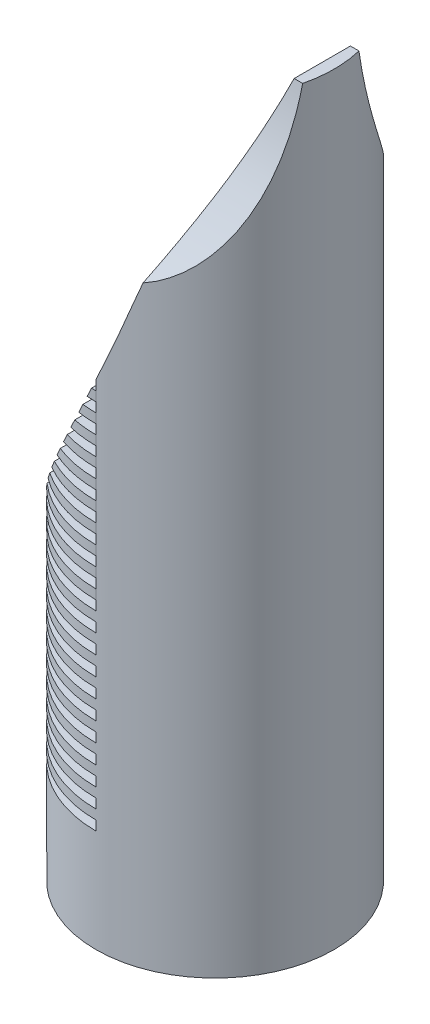
SolidWorks part; units mm, degrees
ref_plane "Front Plane" through (0, 0, 0) normal (0, 0, 1) x (1, 0, 0)
ref_plane "Top Plane" through (0, 0, 0) normal (0, 1, 0) x (1, 0, 0)
ref_plane "Right Plane" through (0, 0, 0) normal (1, 0, 0) x (0, 0, -1)
sketch "Sketch1" plane through (0, 0, 0) normal (0, 1, 0) x (1, 0, 0)
  circle A0 centre (0, 0) radius 2.5
  circle A1 centre (0, 0) radius 0.5
  dimension "D1" = 5
  dimension "D2" = 1
extrude "Boss-Extrude1" add sketch "Sketch1" along normal blind 2
sketch "Sketch2" plane through (0, 2, 0) normal (0, 1, 0) x (1, 0, 0)
  circle A0 centre (0, 0) radius 2.5
  dimension "D1" = 5
extrude "Boss-Extrude2" add sketch "Sketch2" along normal blind 14
sketch "Sketch3" plane through (0, 0, 0) normal (0, 0, 1) x (1, 0, 0)
  line L0 (0, 16) -> (0, 6) construction
  line L1 (2.5, 16) -> (-2.5, 16) construction
  line L2 (-2.5, 16) -> (-2.5, 0) construction
  line L3 (1.5, 16) -> (-2.5, 16)
  line L4 (-2.5, 16) -> (-2.5, 6)
  spline S0 degree 3 poles (1.5, 16) (1.3118, 12.2915) (-0.5237, 8.9999) (-2.5, 6) knots 0 0 0 0 1 1 1 1
  dimension "D1" = 10
extrude "Cut-Extrude1" cut sketch "Sketch3" against normal through all both and the other way through all
sketch "Sketch4" plane through (0, 2, 0) normal (0, -1, 0) x (1, 0, 0)
  circle A0 centre (0, 0) radius 0.5
extrude "Cut-Extrude2" cut sketch "Sketch4" against normal blind 7
sketch "Sketch5" plane through (0, 0, 0) normal (1, 0, 0) x (0, 0, -1)
  line L0 (0, 0) -> (0, 10.3563) construction
  line L1 (-2.5, 0) -> (2.5, 0) construction
  line L2 (3.1377, 10.1563) -> (0.25, 10.1563)
  line L3 (0.25, 0) -> (0.25, 10.3563)
  line L4 (-0.25, 0) -> (-0.25, 10.3563)
  line L5 (0.25, 10.3563) -> (3.1377, 10.3563)
  line L6 (3.1377, 9.3563) -> (0.25, 9.3563)
  line L7 (0.25, 0) -> (0.25, 16) construction
  line L8 (0, 0) -> (0, 16) construction
  line L9 (-0.25, 0) -> (-0.25, 16) construction
  line L10 (3.1377, 10.3563) -> (3.1377, 10.1563)
  line L11 (0.25, 9.5563) -> (3.1377, 9.5563)
  line L12 (3.1377, 9.5563) -> (3.1377, 9.3563)
  line L13 (3.1377, 9.7563) -> (0.25, 9.7563)
  line L14 (0.25, 9.9563) -> (3.1377, 9.9563)
  line L15 (3.1377, 9.9563) -> (3.1377, 9.7563)
  line L16 (3.1377, 6.1563) -> (0.25, 6.1563)
  line L17 (0.25, 6.3563) -> (3.1377, 6.3563)
  line L18 (3.1377, 6.3563) -> (3.1377, 6.1563)
  line L19 (3.1377, 6.9563) -> (0.25, 6.9563)
  line L20 (0.25, 7.1563) -> (3.1377, 7.1563)
  line L21 (3.1377, 7.1563) -> (3.1377, 6.9563)
  line L22 (3.1377, 7.3563) -> (0.25, 7.3563)
  line L23 (0.25, 7.5563) -> (3.1377, 7.5563)
  line L24 (3.1377, 7.5563) -> (3.1377, 7.3563)
  line L25 (3.1377, 7.7563) -> (0.25, 7.7563)
  line L26 (0.25, 7.9563) -> (3.1377, 7.9563)
  line L27 (3.1377, 7.9563) -> (3.1377, 7.7563)
  line L28 (3.1377, 8.5563) -> (0.25, 8.5563)
  line L29 (0.25, 8.7563) -> (3.1377, 8.7563)
  line L30 (3.1377, 8.7563) -> (3.1377, 8.5563)
  line L31 (3.1377, 8.9563) -> (0.25, 8.9563)
  line L32 (0.25, 9.1563) -> (3.1377, 9.1563)
  line L33 (3.1377, 9.1563) -> (3.1377, 8.9563)
  line L34 (3.1377, 8.1563) -> (0.25, 8.1563)
  line L35 (0.25, 8.3563) -> (3.1377, 8.3563)
  line L36 (3.1377, 8.3563) -> (3.1377, 8.1563)
  line L37 (3.1377, 2.9563) -> (0.25, 2.9563)
  line L38 (0.25, 3.1563) -> (3.1377, 3.1563)
  line L39 (3.1377, 3.1563) -> (3.1377, 2.9563)
  line L40 (3.1377, 6.5563) -> (0.25, 6.5563)
  line L41 (0.25, 6.7563) -> (3.1377, 6.7563)
  line L42 (3.1377, 6.7563) -> (3.1377, 6.5563)
  line L43 (3.1377, 3.3563) -> (0.25, 3.3563)
  line L44 (0.25, 3.5563) -> (3.1377, 3.5563)
  line L45 (3.1377, 3.5563) -> (3.1377, 3.3563)
  line L46 (3.1377, 4.9563) -> (0.25, 4.9563)
  line L47 (0.25, 5.1563) -> (3.1377, 5.1563)
  line L48 (3.1377, 5.1563) -> (3.1377, 4.9563)
  line L49 (3.1377, 4.5563) -> (0.25, 4.5563)
  line L50 (0.25, 4.7563) -> (3.1377, 4.7563)
  line L51 (3.1377, 4.7563) -> (3.1377, 4.5563)
  line L52 (3.1377, 3.7563) -> (0.25, 3.7563)
  line L53 (0.25, 3.9563) -> (3.1377, 3.9563)
  line L54 (3.1377, 3.9563) -> (3.1377, 3.7563)
  line L55 (3.1377, 4.1563) -> (0.25, 4.1563)
  line L56 (0.25, 4.3563) -> (3.1377, 4.3563)
  line L57 (3.1377, 4.3563) -> (3.1377, 4.1563)
  line L58 (3.1377, 5.3563) -> (0.25, 5.3563)
  line L59 (0.25, 5.5563) -> (3.1377, 5.5563)
  line L60 (3.1377, 5.5563) -> (3.1377, 5.3563)
  line L61 (-3.1377, 2.7563) -> (-3.1377, 2.5563)
  line L62 (-0.25, 2.7563) -> (-3.1377, 2.7563)
  line L63 (-3.1377, 2.5563) -> (-0.25, 2.5563)
  line L64 (-3.1377, 2.3563) -> (-3.1377, 2.1563)
  line L65 (-0.25, 2.3563) -> (-3.1377, 2.3563)
  line L66 (-3.1377, 2.1563) -> (-0.25, 2.1563)
  line L67 (3.1377, 5.7563) -> (0.25, 5.7563)
  line L68 (0.25, 5.9563) -> (3.1377, 5.9563)
  line L69 (3.1377, 5.9563) -> (3.1377, 5.7563)
  line L70 (-3.1377, 5.9563) -> (-3.1377, 5.7563)
  line L71 (-0.25, 5.9563) -> (-3.1377, 5.9563)
  line L72 (-3.1377, 5.7563) -> (-0.25, 5.7563)
  line L73 (3.1377, 2.1563) -> (0.25, 2.1563)
  line L74 (0.25, 2.3563) -> (3.1377, 2.3563)
  line L75 (3.1377, 2.3563) -> (3.1377, 2.1563)
  line L76 (3.1377, 2.5563) -> (0.25, 2.5563)
  line L77 (0.25, 2.7563) -> (3.1377, 2.7563)
  line L78 (3.1377, 2.7563) -> (3.1377, 2.5563)
  line L79 (-3.1377, 5.5563) -> (-3.1377, 5.3563)
  line L80 (-0.25, 5.5563) -> (-3.1377, 5.5563)
  line L81 (-3.1377, 5.3563) -> (-0.25, 5.3563)
  line L82 (-3.1377, 4.3563) -> (-3.1377, 4.1563)
  line L83 (-0.25, 4.3563) -> (-3.1377, 4.3563)
  line L84 (-3.1377, 4.1563) -> (-0.25, 4.1563)
  line L85 (-3.1377, 3.9563) -> (-3.1377, 3.7563)
  line L86 (-0.25, 3.9563) -> (-3.1377, 3.9563)
  line L87 (-3.1377, 3.7563) -> (-0.25, 3.7563)
  line L88 (-3.1377, 4.7563) -> (-3.1377, 4.5563)
  line L89 (-0.25, 4.7563) -> (-3.1377, 4.7563)
  line L90 (-3.1377, 4.5563) -> (-0.25, 4.5563)
  line L91 (-3.1377, 5.1563) -> (-3.1377, 4.9563)
  line L92 (-0.25, 5.1563) -> (-3.1377, 5.1563)
  line L93 (-3.1377, 4.9563) -> (-0.25, 4.9563)
  line L94 (-3.1377, 3.5563) -> (-3.1377, 3.3563)
  line L95 (-0.25, 3.5563) -> (-3.1377, 3.5563)
  line L96 (-3.1377, 3.3563) -> (-0.25, 3.3563)
  line L97 (-3.1377, 6.7563) -> (-3.1377, 6.5563)
  line L98 (-0.25, 6.7563) -> (-3.1377, 6.7563)
  line L99 (-3.1377, 6.5563) -> (-0.25, 6.5563)
  line L100 (-3.1377, 3.1563) -> (-3.1377, 2.9563)
  line L101 (-0.25, 3.1563) -> (-3.1377, 3.1563)
  line L102 (-3.1377, 2.9563) -> (-0.25, 2.9563)
  line L103 (-3.1377, 8.3563) -> (-3.1377, 8.1563)
  line L104 (-0.25, 8.3563) -> (-3.1377, 8.3563)
  line L105 (-3.1377, 8.1563) -> (-0.25, 8.1563)
  line L106 (-3.1377, 9.1563) -> (-3.1377, 8.9563)
  line L107 (-0.25, 9.1563) -> (-3.1377, 9.1563)
  line L108 (-3.1377, 8.9563) -> (-0.25, 8.9563)
  line L109 (-3.1377, 8.7563) -> (-3.1377, 8.5563)
  line L110 (-0.25, 8.7563) -> (-3.1377, 8.7563)
  line L111 (-3.1377, 8.5563) -> (-0.25, 8.5563)
  line L112 (-3.1377, 7.9563) -> (-3.1377, 7.7563)
  line L113 (-0.25, 7.9563) -> (-3.1377, 7.9563)
  line L114 (-3.1377, 7.7563) -> (-0.25, 7.7563)
  line L115 (-3.1377, 7.5563) -> (-3.1377, 7.3563)
  line L116 (-0.25, 7.5563) -> (-3.1377, 7.5563)
  line L117 (-3.1377, 7.3563) -> (-0.25, 7.3563)
  line L118 (-3.1377, 7.1563) -> (-3.1377, 6.9563)
  line L119 (-0.25, 7.1563) -> (-3.1377, 7.1563)
  line L120 (-3.1377, 6.9563) -> (-0.25, 6.9563)
  line L121 (-3.1377, 6.3563) -> (-3.1377, 6.1563)
  line L122 (-0.25, 6.3563) -> (-3.1377, 6.3563)
  line L123 (-3.1377, 6.1563) -> (-0.25, 6.1563)
  line L124 (-3.1377, 9.9563) -> (-3.1377, 9.7563)
  line L125 (-0.25, 9.9563) -> (-3.1377, 9.9563)
  line L126 (-3.1377, 9.7563) -> (-0.25, 9.7563)
  line L127 (-3.1377, 9.5563) -> (-3.1377, 9.3563)
  line L128 (-0.25, 9.5563) -> (-3.1377, 9.5563)
  line L129 (-3.1377, 10.3563) -> (-3.1377, 10.1563)
  line L130 (-3.1377, 9.3563) -> (-0.25, 9.3563)
  line L131 (-0.25, 10.3563) -> (-3.1377, 10.3563)
  line L132 (-3.1377, 10.1563) -> (-0.25, 10.1563)
  dimension "D3" = 0.2
  dimension "D4" = 0.2
  dimension "D5" = 0.2
  dimension "D6" = 0.2
  dimension "D1" = 0.2
  dimension "D7" = 0.2
  dimension "D8" = 0.2
  dimension "D9" = 0.2
  dimension "D10" = 0.2
  dimension "D11" = 0.2
  dimension "D12" = 0.2
  dimension "D13" = 0.2
  dimension "D14" = 0.2
  dimension "D15" = 0.2
  dimension "D16" = 0.2
  dimension "D17" = 0.2
  dimension "D18" = 0.2
  dimension "D19" = 0.2
  dimension "D20" = 0.2
  dimension "D21" = 0.2
  dimension "D22" = 0.2
  dimension "D23" = 0.2
  dimension "D24" = 0.2
  dimension "D25" = 0.2
  dimension "D26" = 0.2
  dimension "D27" = 0.2
  dimension "D28" = 0.2
  dimension "D29" = 0.2
  dimension "D32" = 0.2
  dimension "D33" = 0.2
  dimension "D34" = 0.2
  dimension "D35" = 0.2
  dimension "D36" = 0.2
  dimension "D37" = 0.2
  dimension "D38" = 0.2
  dimension "D39" = 0.2
  dimension "D40" = 0.2
  dimension "D42" = 0.2
  dimension "D43" = 0.2
  dimension "D45" = 0.2
  dimension "D46" = 0.2
extrude "Cut-Extrude3" cut sketch "Sketch5" against normal blind 7 contours L64 L66 L4 L65 | L61 L63 L4 L62 | L100 L102 L4 L101 | L94 L96 L4 L95 | L75 L74 L3 L73 | L78 L77 L3 L76 | L39 L38 L3 L37 | L45 L44 L3 L43 | L54 L53 L3 L52 | L57 L56 L3 L55 | L51 L50 L3 L49 | L85 L87 L4 L86 | L82 L84 L4 L83 | L88 L90 L4 L89 | L91 L93 L4 L92 | L48 L47 L3 L46 | L60 L59 L3 L58 | L69 L68 L3 L67 | L18 L17 L3 L16 | L42 L41 L3 L40 | L21 L20 L3 L19 | L24 L23 L3 L22 | L79 L81 L4 L80 | L70 L72 L4 L71 | L121 L123 L4 L122 | L97 L99 L4 L98 | L118 L120 L4 L119 | L115 L117 L4 L116 | L112 L114 L4 L113 | L103 L105 L4 L104 | L109 L111 L4 L110 | L106 L108 L4 L107 | L127 L130 L4 L128 | L124 L126 L4 L125 | L129 L132 L4 L131 | L27 L26 L3 L25 | L36 L35 L3 L34 | L30 L29 L3 L28 | L33 L32 L3 L31 | L12 L11 L3 L6 | L15 L14 L3 L13 | L10 L5 L3 L2 region at (0, 2.2563, -1.6939) region at (0, 2.6563, -1.6939) region at (0, 3.0563, -1.6939) region at (0, 3.4563, -1.6939) region at (0, 3.8563, -1.6939) region at (0, 4.2563, -1.6939) region at (0, 4.6563, -1.6939) region at (0, 5.0563, -1.6939) region at (0, 5.4563, -1.6939) region at (0, 5.8563, -1.6939) region at (0, 6.2563, -1.6939) region at (0, 6.6563, -1.6939) region at (0, 7.0563, -1.6939) region at (0, 7.4563, -1.6939) region at (0, 7.8563, -1.6939) region at (0, 8.2563, -1.6939) region at (0, 8.6563, -1.6939) region at (0, 9.0563, -1.6939) region at (0, 9.4563, -1.6939) region at (0, 9.8563, -1.6939) region at (0, 10.2563, -1.6939) region at (0, 2.2563, 1.6939) region at (0, 10.2563, 1.6939) region at (0, 9.8563, 1.6939) region at (0, 9.4563, 1.6939) region at (0, 9.0563, 1.6939) region at (0, 8.6563, 1.6939) region at (0, 8.2563, 1.6939) region at (0, 7.8563, 1.6939) region at (0, 7.4563, 1.6939) region at (0, 7.0563, 1.6939) region at (0, 6.6563, 1.6939) region at (0, 6.2563, 1.6939) region at (0, 5.8563, 1.6939) region at (0, 5.4563, 1.6939) region at (0, 5.0563, 1.6939) region at (0, 4.6563, 1.6939) region at (0, 4.2563, 1.6939) region at (0, 3.8563, 1.6939) region at (0, 3.4563, 1.6939) region at (0, 3.0563, 1.6939) region at (0, 2.6563, 1.6939)
sketch "Sketch6" plane through (0, 0, 0) normal (1, 0, 0) x (0, 0, -1)
  line L0 (2, 16) -> (-2, 16) construction
  line L1 (0, 16) -> (0, 10.9985) construction
  line L2 (-0.5905, 16) -> (-2.3585, 16)
  line L3 (-2.3585, 16) -> (-2.3585, 12.4584)
  line L4 (2.3585, 12.4584) -> (2.3585, 16.1645)
  line L5 (2.3585, 16.1645) -> (0.5905, 16)
  spline S0 degree 2 poles (-0.5905, 16) (-0.9594, 13.9651) (-2.3585, 12.4584) knots 0 0 0 1 1 1
  spline S1 degree 3 poles (-2, 16) (-2.0378, 15.0084) (-2.1646, 14.0498) (-2.3389, 12.6388) (-2.3943, 12.1711) (-2.4748, 11.2506) (-2.5, 10.7995) (-2.5, 10.3561) knots 0 0 0 0 0.5 0.5 0.75 0.75 1 1 1 1 construction
  spline S2 degree 2 poles (0.5905, 16) (0.9594, 13.9651) (2.3585, 12.4584) knots 0 0 0 1 1 1
extrude "Cut-Extrude4" cut sketch "Sketch6" along normal blind 10
sketch "Sketch7" plane through (0, 0, 0) normal (1, 0, 0) x (0, 0, -1)
  line L0 (0, 16) -> (0, 11.4523) construction
  line L1 (0.5905, 16) -> (-0.5905, 16) construction
chamfer "Chamfer1" distance 0.75 angle 68 1 edges at (1.5, 16, 0) first distance on face at (1.9823, 16, 0)
fillet "Fillet1" radius 50 1 edges at (0.8659, 12.5742, 0)
